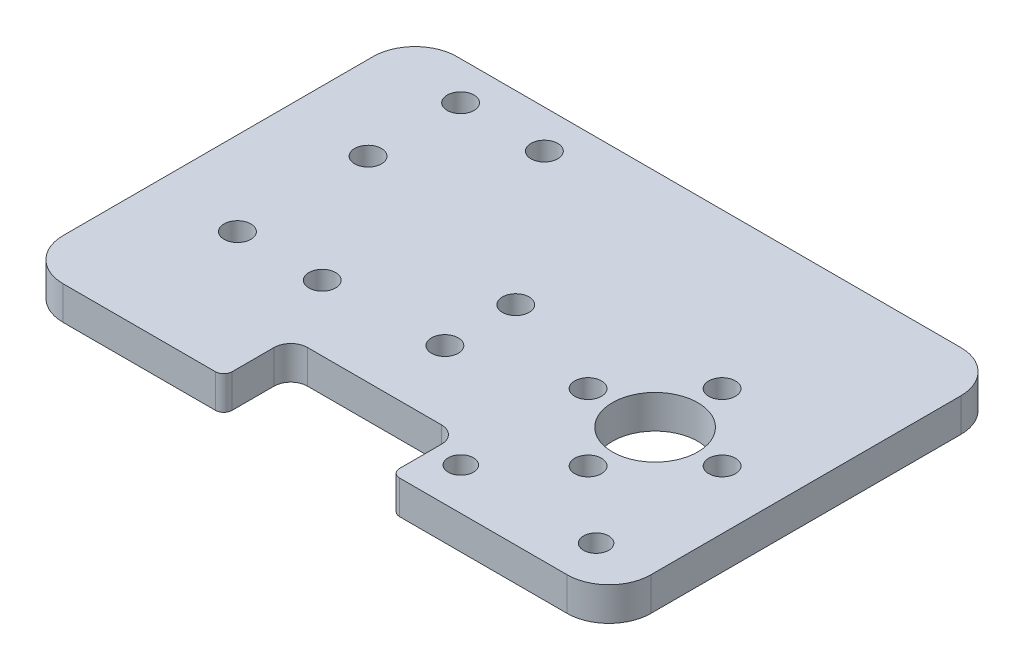
SolidWorks part; units mm, degrees
material "6061 合金"
ref_plane "前视基准面" through (0, 0, 0) normal (0, 0, 1) x (1, 0, 0)
ref_plane "上视基准面" through (0, 0, 0) normal (0, 1, 0) x (1, 0, 0)
ref_plane "右视基准面" through (0, 0, 0) normal (1, 0, 0) x (0, 0, -1)
sketch "草图1" plane through (0, 0, 0) normal (0, 1, 0) x (1, 0, 0)
  line L1 (-90, -21.5) -> (90, -21.5)
  line L2 (-90, -21.5) -> (-90, 21.5)
  line L3 (-90, 21.5) -> (90, 21.5)
  line L4 (90, -21.5) -> (90, 21.5)
  line L5 (0, 21.5) -> (0, -21.5) construction
  line L6 (-90, 0) -> (90, 0) construction
  point P0 (0, 0)
  dimension "D1" = 43
  dimension "D2" = 180
extrude "主体" add sketch "草图1" along normal blind 4
sketch "草图2" plane through (0, 4, 0) normal (0, 1, 0) x (1, 0, 0)
  line L0 (-1000, -5) -> (49000, -5) construction
  line L1 (0, -1000) -> (0, 49000) construction
  circle A0 centre (55, -5) radius 5.1
  circle A1 centre (63, -5) radius 1.6
  circle A2 centre (55, -13) radius 1.6
  circle A3 centre (47, -5) radius 1.6
  circle A4 centre (55, 3) radius 1.6
  point P18 (55, -5)
  dimension "D1" = 55
  dimension "D2" = 10.2
  dimension "D3" = 3.2
  dimension "D4" = 8
  dimension "D6" = 5
  dimension "D5" = 4
extrude "丝杆螺母" cut sketch "草图2" against normal through all
sketch "草图3" plane through (0, 4, 0) normal (0, 1, 0) x (1, 0, 0)
  line L0 (-90, -21.5) -> (90, -21.5) construction
  line L1 (-12, -36) -> (12, -36)
  line L2 (-12, -36) -> (-12, -16)
  line L3 (-12, -16) -> (12, -16)
  line L4 (12, -36) -> (12, -16)
  line L5 (0, -16) -> (0, -36) construction
  line L6 (-12, -26) -> (12, -26) construction
  point P0 (0, -26)
  dimension "D1" = 5.5
  dimension "D2" = 24
  dimension "D3" = 20
extrude "导轨1" [suppressed] cut sketch "草图3" against normal through all
sketch "草图5" [suppressed] plane through (0, 3, 0) normal (0, 1, 0) x (1, 0, 0)
  line L0 (-11.5, -10.5) -> (11.5, -10.5) construction
  line L1 (-3, -16.5) -> (3, -16.5)
  line L2 (-3, -16.5) -> (-3, -10.5)
  line L3 (-3, -10.5) -> (3, -10.5)
  line L4 (3, -16.5) -> (3, -10.5)
  line L5 (0, -10.5) -> (0, -16.5) construction
  line L6 (-3, -13.5) -> (3, -13.5) construction
  point P0 (0, -13.5)
  dimension "D1" = 6
  dimension "D2" = 6
extrude "导轨2" [suppressed] add sketch "草图5" against normal through all
sketch "草图6" [suppressed] plane through (0, 3, 0) normal (0, 1, 0) x (1, 0, 0)
  line L1 (-11.5, -10.5) -> (-3, -10.5) construction
  line L2 (-3, -10.5) -> (-3, -16.5) construction
  line L4 (3, -10.5) -> (11.5, -10.5) construction
  line L5 (3, -16.5) -> (3, -10.5) construction
  circle A0 centre (-4.5, -10.5) radius 1.5
  circle A2 centre (4.5, -10.5) radius 1.5
  dimension "D1" = 3
extrude "辅助铣削" [suppressed] cut sketch "草图6" against normal through all
fillet "圆角1" [suppressed] radius 1.5
sketch "草图7" plane through (0, 4, 0) normal (0, 1, 0) x (1, 0, 0)
  line L0 (0, -1000) -> (0, 49000) construction
  line L1 (-1000, 0) -> (49000, 0) construction
  line L2 (-50, -1000) -> (-50, 49000) construction
  line L3 (-50, -1000) -> (-50, 49000) construction
  circle A1 centre (-50, 0) radius 7.6
  circle A2 centre (-62, 0) radius 1.6
  circle A3 centre (-38, 0) radius 1.6
  circle A4 centre (-50, 12) radius 1.6
  circle A5 centre (-50, -12) radius 1.6
  dimension "D1" = 50
  dimension "D2" = 15.2
  dimension "D3" = 24
  dimension "3.2" = 3.2
  dimension "D4" = 24
extrude "光杆" [suppressed] cut sketch "草图7" against normal through all both and the other way through all
sketch "草图8" plane through (0, 4, 0) normal (0, 1, 0) x (1, 0, 0)
  line L0 (0, -1000) -> (0, 49000) construction
  line L1 (-1000, 0) -> (49000, 0) construction
  line L2 (-90, -21.5) -> (90, -21.5) construction
  line L3 (37.5, -28) -> (72.5, -28)
  line L4 (37.5, -28) -> (37.5, -18)
  line L5 (37.5, -18) -> (72.5, -18)
  line L6 (72.5, -28) -> (72.5, -18)
  line L7 (55, -18) -> (55, -28) construction
  line L8 (37.5, -23) -> (72.5, -23) construction
  line L9 (55, -1000) -> (55, 49000) construction
  point P4 (55, -23)
  dimension "D1" = 3.5
  dimension "D2" = 35
  dimension "D3" = 10
extrude "板接件" [suppressed] cut sketch "草图8" against normal through all
sketch "草图9" [suppressed] plane through (0, 3, 0) normal (0, 1, 0) x (1, 0, 0)
  line L0 (-90, 15) -> (-90, -15) construction
  line L1 (-90, 15) -> (-20, 15)
  line L2 (-90, 15) -> (-90, -15)
  line L3 (-90, -15) -> (-20, -15)
  line L4 (-20, 15) -> (-20, -15)
  line L6 (90, 15) -> (-90, 15) construction
  line L7 (-90, -15) -> (-12, -15) construction
  line L8 (-12, -15) -> (-12, -9.5) construction
  dimension "D1" = 8
extrude "去除辅助板" [suppressed] cut sketch "草图9" against normal through all
sketch "草图10" plane through (0, 4, 0) normal (0, 1, 0) x (1, 0, 0)
  line L0 (90, 21.5) -> (-90, 21.5) construction
  line L1 (90, 21.5) -> (70, 21.5)
  line L2 (90, 21.5) -> (90, -21.5)
  line L3 (90, -21.5) -> (70, -21.5)
  line L4 (70, 21.5) -> (70, -21.5)
  line L5 (90, -21.5) -> (90, 21.5) construction
  line L6 (-90, -21.5) -> (90, -21.5) construction
  dimension "D1" = 20
extrude "限位开关" cut sketch "草图10" against normal through all
sketch "草图11" plane through (0, 4, 0) normal (0, 1, 0) x (1, 0, 0)
  line L0 (-90, -21.5) -> (70, -21.5) construction
  line L1 (-90, 21.5) -> (-108, 21.5)
  line L2 (-90, 21.5) -> (-90, -21.5)
  line L3 (-90, -21.5) -> (-108, -21.5)
  line L4 (-108, 21.5) -> (-108, -21.5)
  dimension "D1" = 18
extrude "延长" add sketch "草图11" against normal through all
sketch "草图12" plane through (0, 4, 0) normal (0, 1, 0) x (1, 0, 0)
  line L0 (-88, -1003.0375) -> (-88, 48996.9625) construction
  line L1 (-108, 21.5) -> (-108, -21.5) construction
  line L2 (-108, -21.5) -> (70, -21.5) construction
  line L3 (-108, -28) -> (-68, -28)
  line L4 (-108, -28) -> (-108, -15)
  line L5 (-108, -15) -> (-68, -15)
  line L6 (-68, -28) -> (-68, -15)
  line L7 (-88, -15) -> (-88, -28) construction
  line L8 (-108, -21.5) -> (-68, -21.5) construction
  point P4 (-88, -21.5)
  dimension "D1" = 20
  dimension "D2" = 40
  dimension "8" = 13
extrude "导轨3" cut sketch "草图12" against normal blind 10
sketch "草图13" plane through (0, 4, 0) normal (0, 1, 0) x (1, 0, 0)
  line L0 (-68, -21.5) -> (70, -21.5) construction
  line L1 (50, -51.5) -> (60, -51.5)
  line L2 (50, -51.5) -> (50, -21.5)
  line L3 (50, -21.5) -> (60, -21.5)
  line L4 (60, -51.5) -> (60, -21.5)
  line L5 (55, -21.5) -> (55, -51.5) construction
  line L6 (50, -36.5) -> (60, -36.5) construction
  circle A1 centre (63, -5) radius 1.6 construction
  circle A2 centre (47, -5) radius 1.6 construction
  point P0 (55, -36.5)
  dimension "D1" = 30
  dimension "D2" = 10
extrude "引出" [suppressed] add sketch "草图13" against normal through all
sketch "草图14" plane through (0, 4, 0) normal (0, 1, 0) x (1, 0, 0)
  line L0 (55, -994.9) -> (55, 49005.1) construction
  line L1 (-68, -21.5) -> (70, -21.5) construction
  circle A1 centre (46, -18.5) radius 1.6
  circle A3 centre (47, -5) radius 1.6 construction
  circle A4 centre (63, -5) radius 1.6 construction
  circle A5 centre (64, -18.5) radius 1.6
  dimension "D1" = 3.2
  dimension "D2" = 3
  dimension "D3" = 18
extrude "引出板" cut sketch "草图14" against normal blind 10
sketch "草图15" plane through (0, 4, 0) normal (0, 1, 0) x (1, 0, 0)
  line L0 (-68, -15) -> (-108, -15) construction
  line L1 (-108, -16) -> (-68, -16) construction
  line L2 (-108, -16) -> (-108, 4) construction
  line L3 (-108, 4) -> (-68, 4) construction
  line L4 (-68, -16) -> (-68, 4) construction
  line L5 (-88, 4) -> (-88, -16) construction
  line L6 (-108, -6) -> (-68, -6) construction
  line L7 (-108, 21.5) -> (-108, -15) construction
  circle A0 centre (-102.9, 0.5) radius 1.6 construction
  circle A1 centre (-102.9, -12.5) radius 1.6 construction
  circle A2 centre (-73.1, -12.5) radius 1.6 construction
  circle A3 centre (-73.1, 0.5) radius 1.6 construction
  circle A4 centre (-102.9, 3.25) radius 1.6
  circle A5 centre (-73.1, 3.25) radius 1.6
  point P0 (-88, -6)
  dimension "D4" = 3.2
  dimension "D5" = 5.1
  dimension "D6" = 13
  dimension "D8" = 2.75
  dimension "D1" = 20
  dimension "D2" = 1
  dimension "D3" = 40
  dimension "D7" = 2
extrude "角铝" cut sketch "草图15" against normal through all
ref_plane "沉头基准" through (0, 0, -3.25) normal (0, 0, 1) x (1, 0, 0)
sketch "草图16" plane through (0, 0, -3.25) normal (0, 0, 1) x (1, 0, 0)
  line L0 (-102.9, -994.0717) -> (-102.9, 49005.9283) construction
  line L2 (-102.9, 0) -> (-99.7, 0)
  line L3 (70, 0) -> (-108, 0) construction
  line L4 (-99.7, 0) -> (-101.3, 1.6)
  line L5 (-101.3, 1.6) -> (-102.9, 1.6)
  line L6 (-102.9, 1.6) -> (-102.9, 0)
  line L7 (-108, 0) -> (-108, 4) construction
  dimension "D1" = 5.1
  dimension "D2" = 1.6
  dimension "D3" = 1.6
  dimension "D4" = 3.2
revolve "沉头" cut sketch "草图16" angle 360 about L0
pattern_linear "沉头阵列" count 2 spacing 29.8 along (1, 0, 0) of "沉头"
sketch "草图17" plane through (0, 0, 0) normal (0, -1, 0) x (1, 0, 0)
  line L0 (-88, -992.5571) -> (-88, 49007.4429) construction
  line L9 (-104.45, 3.75) -> (-101.35, 3.75)
  line L10 (-101.35, 6.75) -> (-101.35, 9.75)
  line L11 (-104.45, 9.75) -> (-104.45, 6.75)
  line L12 (-101.35, 12.75) -> (-104.45, 12.75)
  line L17 (-1104, -3.25) -> (48896, -3.25) construction
  line L18 (-108, -21.5) -> (-108, 15) construction
  line L19 (-102.9, -1003.25) -> (-102.9, 48996.75) construction
  line L20 (-104.45, -16.25) -> (-104.45, -13.25)
  line L21 (-101.35, -19.25) -> (-104.45, -19.25)
  line L22 (-101.35, -13.25) -> (-101.35, -16.25)
  line L23 (-104.45, -10.25) -> (-101.35, -10.25)
  line L24 (-71.55, -16.25) -> (-71.55, -13.25)
  line L25 (-74.65, -19.25) -> (-71.55, -19.25)
  line L26 (-74.65, -13.25) -> (-74.65, -16.25)
  line L27 (-71.55, -10.25) -> (-74.65, -10.25)
  line L28 (-71.55, 9.75) -> (-71.55, 6.75)
  line L29 (-74.65, 12.75) -> (-71.55, 12.75)
  line L30 (-74.65, 6.75) -> (-74.65, 9.75)
  line L31 (-71.55, 3.75) -> (-74.65, 3.75)
  circle A0 centre (-102.9, -3.25) radius 1.6 construction
  circle A2 centre (-73.1, -3.25) radius 1.6 construction
  circle A11 centre (-102.9, -3.25) radius 1.6 construction
  arc A12 (-104.45, 6.75) -> (-104.45, 3.75) centre (-104.45, 5.25) ccw
  arc A13 (-104.45, 12.75) -> (-104.45, 9.75) centre (-104.45, 11.25) ccw
  arc A14 (-101.35, 9.75) -> (-101.35, 12.75) centre (-101.35, 11.25) ccw
  arc A15 (-101.35, 3.75) -> (-101.35, 6.75) centre (-101.35, 5.25) ccw
  arc A20 (-104.45, -13.25) -> (-104.45, -10.25) centre (-104.45, -11.75) cw
  arc A21 (-104.45, -19.25) -> (-104.45, -16.25) centre (-104.45, -17.75) cw
  arc A22 (-101.35, -16.25) -> (-101.35, -19.25) centre (-101.35, -17.75) cw
  arc A23 (-101.35, -10.25) -> (-101.35, -13.25) centre (-101.35, -11.75) cw
  arc A24 (-71.55, -19.25) -> (-71.55, -16.25) centre (-71.55, -17.75) ccw
  arc A25 (-74.65, -16.25) -> (-74.65, -19.25) centre (-74.65, -17.75) ccw
  arc A26 (-74.65, -10.25) -> (-74.65, -13.25) centre (-74.65, -11.75) ccw
  arc A27 (-71.55, -13.25) -> (-71.55, -10.25) centre (-71.55, -11.75) ccw
  arc A28 (-71.55, 6.75) -> (-71.55, 3.75) centre (-71.55, 5.25) cw
  arc A29 (-71.55, 12.75) -> (-71.55, 9.75) centre (-71.55, 11.25) cw
  arc A30 (-74.65, 9.75) -> (-74.65, 12.75) centre (-74.65, 11.25) cw
  arc A31 (-74.65, 3.75) -> (-74.65, 6.75) centre (-74.65, 5.25) cw
  dimension "D1" = 3.2
  dimension "D5" = 1.5
  dimension "D2" = 14
  dimension "D3" = 9
  dimension "D4" = 3.1
  dimension "D6" = 20
extrude "榫卯" cut sketch "草图17" against normal through all
sketch "草图19" plane through (0, 4, 0) normal (0, 1, 0) x (1, 0, 0)
  line L0 (70, 21.5) -> (-108, 21.5) construction
  line L1 (-4, 21.5) -> (-108, 21.5)
  line L2 (-4, 21.5) -> (-4, -21.5)
  line L3 (-4, -21.5) -> (-108, -21.5)
  line L4 (-108, 21.5) -> (-108, -21.5)
  line L5 (-68, -21.5) -> (70, -21.5) construction
  line L6 (-108, 21.5) -> (-108, -15) construction
  line L7 (70, 21.5) -> (70, -21.5) construction
  dimension "D1" = 74
extrude "剩丝杆部分" cut sketch "草图19" against normal through all
sketch "草图20" [suppressed] plane through (0, 4, 0) normal (0, 1, 0) x (1, 0, 0)
  line L0 (70, 21.5) -> (-108, 21.5) construction
  line L1 (-71.5, -8.5) -> (70, -8.5) construction
  line L2 (-71.5, -8.5) -> (-71.5, 21.5) construction
  line L3 (-71.5, 21.5) -> (70, 21.5) construction
  line L4 (70, -8.5) -> (70, 21.5) construction
  line L5 (-0.75, 21.5) -> (-0.75, -8.5) construction
  line L6 (-71.5, 6.5) -> (70, 6.5) construction
  line L7 (70, 21.5) -> (70, -21.5) construction
  line L8 (-61.5, 3.35) -> (-61.5, -6.65) construction
  line L9 (-59.25, 3.35) -> (-59.25, -6.65) construction
  line L10 (-63.75, 3.35) -> (-63.75, -6.65) construction
  line L11 (-1111.9835, -1.65) -> (48888.0165, -1.65) construction
  line L12 (-40.5, 3.35) -> (-40.5, -6.65) construction
  line L13 (-38.25, 3.35) -> (-38.25, -6.65) construction
  line L14 (-42.75, 3.35) -> (-42.75, -6.65) construction
  line L15 (-19.5, 3.35) -> (-19.5, -6.65) construction
  line L16 (-17.25, 3.35) -> (-17.25, -6.65) construction
  line L17 (-21.75, 3.35) -> (-21.75, -6.65) construction
  arc A0 (-59.25, 3.35) -> (-63.75, 3.35) centre (-61.5, 3.35) ccw construction
  arc A1 (-63.75, -6.65) -> (-59.25, -6.65) centre (-61.5, -6.65) ccw construction
  arc A2 (-38.25, 3.35) -> (-42.75, 3.35) centre (-40.5, 3.35) ccw construction
  arc A3 (-42.75, -6.65) -> (-38.25, -6.65) centre (-40.5, -6.65) ccw construction
  arc A4 (-17.25, 3.35) -> (-21.75, 3.35) centre (-19.5, 3.35) ccw construction
  arc A5 (-21.75, -6.65) -> (-17.25, -6.65) centre (-19.5, -6.65) ccw construction
  circle A6 centre (-18.1771, 11.1173) radius 2.5
  point P0 (-0.75, 6.5)
  point P13 (-61.5, -1.65)
  point P24 (-40.5, -1.65)
  point P31 (-19.5, -1.65)
  dimension "D6" = 2.25
  dimension "D9" = 5
  dimension "D1" = 141.5
  dimension "D2" = 30
  dimension "D3" = 10
  dimension "D4" = 10
  dimension "D5" = 6.85
  dimension "D8" = 21
  dimension "D7" = 3
extrude "铰链2" [suppressed] cut sketch "草图20" against normal through all
sketch "草图22" [suppressed] plane through (0, 4, 0) normal (0, 1, 0) x (1, 0, 0)
  line L0 (70, 21.5) -> (-108, 21.5) construction
  line L1 (70, 21.5) -> (42, 21.5)
  line L2 (70, 21.5) -> (70, -21.5)
  line L3 (70, -21.5) -> (42, -21.5)
  line L4 (42, 21.5) -> (42, -21.5)
  line L5 (70, 21.5) -> (70, -21.5) construction
  line L6 (-68, -21.5) -> (70, -21.5) construction
  dimension "D1" = 28
extrude "副板部分" [suppressed] cut sketch "草图22" against normal through all
sketch "草图23" [suppressed] plane through (0, 4, 0) normal (0, 1, 0) x (1, 0, 0)
  line L0 (-108, 21.5) -> (-108, -15) construction
  line L1 (-99, -15) -> (-77, -15) construction
  line L2 (-99, -15) -> (-99, 21.5) construction
  line L3 (-99, 21.5) -> (-77, 21.5) construction
  line L4 (-77, -15) -> (-77, 21.5) construction
  line L5 (-88, 21.5) -> (-88, -15) construction
  line L6 (-99, 3.25) -> (-77, 3.25) construction
  line L7 (42, 21.5) -> (-108, 21.5) construction
  line L8 (-68, -15) -> (-108, -15) construction
  line L10 (-98, 0) -> (-78, 0) construction
  line L11 (-98, 0) -> (-98, 15) construction
  line L12 (-98, 15) -> (-78, 15) construction
  line L13 (-78, 0) -> (-78, 15) construction
  line L14 (-88, 15) -> (-88, 0) construction
  line L15 (-98, 7.5) -> (-78, 7.5) construction
  circle A0 centre (-98, 15) radius 1.55 construction
  circle A1 centre (-98, 0) radius 1.55
  circle A2 centre (-78, 0) radius 1.55
  circle A3 centre (-78, 15) radius 1.55 construction
  point P0 (-88, 3.25)
  point P15 (-88, 7.5)
  dimension "D3" = 3.1
  dimension "D4" = 20
  dimension "D5" = 15
  dimension "D1" = 9
  dimension "D2" = 22
  dimension "D6" = 15
extrude "副板固定孔" [suppressed] cut sketch "草图23" against normal through all
fillet "圆角7" [suppressed] radius 10
sketch "草图24" plane through (0, 4, 0) normal (0, 1, 0) x (1, 0, 0)
  line L0 (70, 21.5) -> (-4, 21.5) construction
  line L1 (70, 21.5) -> (70, -21.5) construction
  line L2 (12, -988.5) -> (12, 49011.5) construction
  line L3 (-988, 11.5) -> (49012, 11.5) construction
  line L4 (12.4184, 9.9386) -> (12953.3706, -48286.3527) construction
  circle A1 centre (12, 11.5) radius 2.1
  circle A2 centre (12, 11.5) radius 12.5 construction
  arc A3 (24.5, 11.5) -> (12, -1) centre (12, 11.5) cw construction
  arc A8 (12, -3.1) -> (26.6, 11.5) centre (12, 11.5) ccw
  arc A14 (12, 1.1) -> (22.4, 11.5) centre (12, 11.5) ccw
  arc A15 (12, 1.1) -> (12, -3.1) centre (12, -1) ccw
  arc A16 (26.6, 11.5) -> (22.4, 11.5) centre (24.5, 11.5) ccw
  circle A17 centre (12, 11.5) radius 25 construction
  circle A18 centre (12, -13.5) radius 2.1
  point P15 (20.8388, 2.6612)
  dimension "D1" = 4.2
  dimension "D2" = 10
  dimension "D3" = 58
  dimension "D4" = 25
  dimension "D6" = 2.1
  dimension "D7" = 50
  dimension "D8" = 4.2
  dimension "D5" = 15
sketch "草图25" [suppressed] plane through (0, 4, 0) normal (0, 1, 0) x (1, 0, 0)
  line L0 (-988, 11.5) -> (49012, 11.5) construction
  line L1 (12, -988.5) -> (12, 49011.5) construction
  line L6 (-68, -21.5) -> (42, -21.5)
  line L7 (42, -21.5) -> (42, 21.5)
  line L8 (42, 21.5) -> (-108, 21.5)
  line L9 (-108, 21.5) -> (-108, -15)
  line L10 (-108, -15) -> (-68, -15)
  line L11 (-68, -15) -> (-68, -21.5)
  line L12 (-68, -21.5) -> (42, -21.5) construction
  line L13 (42, -21.5) -> (42, 21.5) construction
  line L14 (42, 21.5) -> (-108, 21.5) construction
  line L15 (-108, 21.5) -> (-108, -15) construction
  line L16 (-108, -15) -> (-68, -15) construction
  line L17 (-68, -15) -> (-68, -21.5) construction
  circle A0 centre (12, 11.5) radius 2.1
  circle A2 centre (12, 11.5) radius 12.5 construction
  circle A14 centre (24.5, 11.5) radius 2.1
  circle A16 centre (12, -1) radius 2.1
  circle A18 centre (12, -13.5) radius 2.1 construction
  arc A19 (12, -13.5) -> (37, 11.5) centre (12, 11.5) ccw construction
  arc A24 (12, -15.6) -> (39.1, 11.5) centre (12, 11.5) ccw
  arc A25 (12, -11.4) -> (34.9, 11.5) centre (12, 11.5) ccw
  arc A26 (12, -11.4) -> (12, -15.6) centre (12, -13.5) ccw
  arc A27 (39.1, 11.5) -> (34.9, 11.5) centre (37, 11.5) ccw
  point P30 (29.6777, -6.1777)
  dimension "D1" = 0
  dimension "D2" = 4.2
  dimension "D3" = 10
  dimension "D4" = 120
  dimension "D5" = 25
  dimension "D6" = 4.2
  dimension "D7" = 25
extrude "螺钉转轴2" [suppressed] cut sketch "草图25" against normal through all contours A16 | A0 | A14 | A25 A27 A24 A26
fillet "圆角8" [suppressed] radius 20
fillet "圆角9" radius 5 4 edges at (70, 2, 21.5) (70, 2, -21.5) (-4, 2, 21.5) (-4, 2, -21.5)
fillet "圆角10" [suppressed] radius 4
sketch "草图27" [suppressed] plane through (0, 4, 0) normal (0, 1, 0) x (1, 0, 0)
  line L0 (38, 21.5) -> (-108, 21.5) construction
  line L1 (-158, 13.5) -> (-18, 13.5)
  line L2 (-158, 13.5) -> (-158, 21.5)
  line L3 (-158, 21.5) -> (-18, 21.5)
  line L4 (-18, 13.5) -> (-18, 21.5)
  line L5 (-88, 21.5) -> (-88, 13.5) construction
  line L6 (-158, 17.5) -> (-18, 17.5) construction
  circle A0 centre (-98, 0) radius 1.55 construction
  circle A1 centre (-78, 0) radius 1.55 construction
  point P0 (-88, 17.5)
  dimension "D1" = 140
  dimension "D2" = 8
extrude "削_翼" [suppressed] cut sketch "草图27" against normal blind 10
ref_axis "沉头轴" [suppressed] through (-78, 0, 0) along (0, 1, 0)
ref_plane "沉头面" [suppressed] through (0, 0, 0) normal (0, 0, 1) x (0, 1, 0)
sketch "草图28" [suppressed] plane through (0, 0, 0) normal (0, 0, 1) x (0, 1, 0)
  line L0 (0, 81.2) -> (3.2, 78)
  line L1 (0, 18) -> (0, 108) construction
  line L2 (0, 78) -> (4, 78) construction
  line L3 (3.2, 78) -> (0, 78)
  line L4 (0, 78) -> (0, 81.2)
  line L5 (-996.1241, 78) -> (49003.8759, 78) construction
  dimension "D1" = 3.2
  dimension "D2" = 3.2
revolve "M3_沉" [suppressed] cut sketch "草图28" angle 360 about L5
pattern_linear "阵列_沉头" [suppressed] count 2 spacing 20 of bodies 140
fillet "圆角5" [suppressed] radius 5
fillet "圆角2" [suppressed] radius 2
sketch "草图29" plane through (0, 4, 0) normal (0, 1, 0) x (1, 0, 0)
  line L0 (1, 21.5) -> (10.8307, 21.5)
  line L1 (65, 21.5) -> (1, 21.5) construction
  line L2 (10.8307, 13.1085) -> (10.8307, 22.6603) construction
  line L3 (10.8307, 21.5) -> (10.8307, -21.5)
  line L4 (1, -21.5) -> (65, -21.5) construction
  line L5 (10.8307, -21.7382) -> (10.8307, -15.5848) construction
  line L6 (10.8307, -21.5) -> (1, -21.5)
  line L7 (1, -21.5) -> (-4.2543, -21.5)
  line L8 (-4.2543, -21.5) -> (-4.2543, 21.5)
  line L9 (-4.2543, 21.5) -> (1, 21.5)
extrude "切除-拉伸1" cut sketch "草图29" against normal through all
sketch "草图30" plane through (0, 4, 0) normal (0, 1, 0) x (1, 0, 0)
  line L0 (10.8307, 21.5) -> (8.8307, 21.5)
  line L1 (10.8307, 21.5) -> (10.8307, -21.5)
  line L2 (10.8307, -21.5) -> (8.8307, -21.5)
  line L3 (8.8307, -21.5) -> (8.8307, 21.5)
extrude "凸台-拉伸1" add sketch "草图30" against normal blind 4
sketch "草图32" plane through (0, 0, 0) normal (0, -1, 0) x (1, 0, 0)
  line L0 (8.8307, -21.5) -> (-0.1693, -21.5)
  line L1 (8.8307, -21.5) -> (8.8307, 21.5)
  line L2 (8.8307, 21.5) -> (-0.1693, 21.5)
  line L3 (-0.1693, 21.5) -> (-0.1693, -21.5)
extrude "凸台-拉伸2" add sketch "草图32" against normal blind 4
fillet "圆角11" radius 5 2 edges at (-0.1693, 2, -21.5) (-0.1693, 2, 21.5)
sketch "草图33" plane through (0, 0, 0) normal (0, -1, 0) x (1, 0, 0)
  line L0 (65, 21.5) -> (65, 25.5) construction
  line L1 (70, 16.5) -> (70, 25.5)
  line L2 (70, 25.5) -> (65, 25.5)
  line L3 (65, 25.5) -> (0, 25.5)
  line L5 (0, 25.5) -> (-0.1693, 25.5)
  line L6 (-0.1693, 25.5) -> (-0.1693, 16.5)
  line L7 (-0.1693, 16.5) -> (70, 16.5)
extrude "凸台-拉伸3" add sketch "草图33" against normal up to surface (4 mm away) up to face at (46, 4, 20.1)
fillet "圆角12" radius 5 2 edges at (-0.1693, 2, 25.5) (70, 2, 25.5)
sketch "草图34" plane through (0, 0, 0) normal (0, -1, 0) x (1, 0, 0)
  circle A0 centre (63.4554, 20.5) radius 1.5
  circle A1 centre (47.3015, 20.5) radius 1.5
extrude "切除-拉伸3" cut sketch "草图34" against normal through all
sketch "草图35" plane through (0, 0, 0) normal (0, -1, 0) x (1, 0, 0)
  circle A0 centre (34, 0.6367) radius 1.6
  circle A1 centre (34, 9.1) radius 1.6
  dimension "D1" = 3.2
  dimension "D2" = 3.2
extrude "切除-拉伸4" cut sketch "草图35" against normal through all
sketch "草图36" plane through (0, 0, 0) normal (0, -1, 0) x (1, 0, 0)
  line L0 (4.8307, -21.5) -> (9.8307, -21.5) construction
  line L1 (65, -21.5) -> (4.8307, -21.5) construction
  line L2 (9.8307, -21.5) -> (9.8307, -5.9) construction
  line L3 (9.8307, -5.9) -> (9.8307, 9.7) construction
  line L4 (9.8307, -16.9489) -> (19.8307, -16.9489) construction
  circle A0 centre (9.8307, -5.9) radius 1.6
  circle A1 centre (9.8307, 9.7) radius 1.6
  circle A2 centre (9.8307, -16.9489) radius 1.6
  circle A3 centre (19.8307, -16.9489) radius 1.6
  dimension "D1" = 3.2
  dimension "D2" = 3.2
  dimension "D3" = 3.2
  dimension "D4" = 3.2
extrude "切除-拉伸5" cut sketch "草图36" against normal through all
sketch "草图37" plane through (0, 4, 0) normal (0, 1, 0) x (1, 0, 0)
  circle A0 centre (19.9251, -9.6642) radius 1.6
  dimension "D1" = 3.2
extrude "切除-拉伸6" cut sketch "草图37" against normal through all
sketch "草图38" plane through (0, 0, 0) normal (0, -1, 0) x (1, 0, 0)
  line L0 (44, 25.5) -> (44, 19.5)
  line L1 (65, 25.5) -> (4.8307, 25.5) construction
  line L2 (42, 17.5) -> (26, 17.5)
  line L3 (24, 19.5) -> (24, 25.5)
  line L4 (24, 25.5) -> (44, 25.5)
  line L5 (70, -16.5) -> (70, 20.5) construction
  arc A0 (44, 19.5) -> (42, 17.5) centre (42, 19.5) cw
  arc A1 (26, 17.5) -> (24, 19.5) centre (26, 19.5) cw
  dimension "D2" = 2
  dimension "D1" = 26
extrude "切除-拉伸7" cut sketch "草图38" against normal through all
fillet "圆角15" radius 1 2 edges at (44, 2, 25.5) (24, 2, 25.5)
